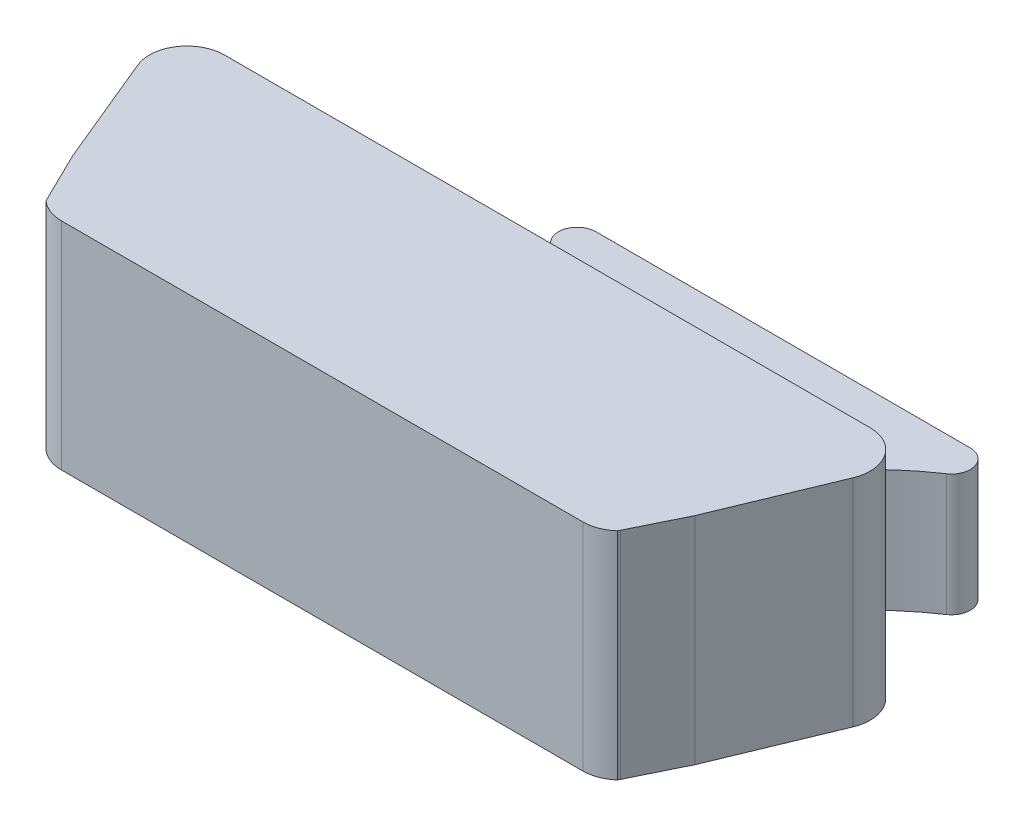
SolidWorks part; units mm, degrees
ref_plane "前视基准面" through (0, 0, 0) normal (0, 0, 1) x (1, 0, 0)
ref_plane "上视基准面" through (0, 0, 0) normal (0, 1, 0) x (1, 0, 0)
ref_plane "右视基准面" through (0, 0, 0) normal (1, 0, 0) x (0, 0, -1)
other "Configuration Table"
sketch "草图1" plane through (0, 0, 0) normal (0, 1, 0) x (1, 0, 0)
  line L0 (0, 0) -> (0, 18.74) construction
  line L1 (-14.3085, 18.74) -> (14.3085, 18.74)
  line L2 (3.9, 4.46) -> (3.9, 0)
  line L3 (-3.9, 0) -> (3.9, 0)
  line L4 (-3.9, 4.46) -> (-3.9, 0)
  arc A0 (14.3085, 18.74) -> (3.9, 4.46) centre (18.9, 4.46) ccw
  arc A1 (-14.3085, 18.74) -> (-3.9, 4.46) centre (-18.9, 4.46) cw
  dimension "D2" = 15
  dimension "D1" = 7.8
  dimension "D3" = 14.28
  dimension "D4" = 18.74
extrude "凸台-拉伸1" add sketch "草图1" along normal blind 6.5
sketch "草图2" plane through (0, 6.5, 0) normal (0, 1, 0) x (1, 0, 0)
  line L0 (9.9174, 1.2346) -> (13.2311, 9.2346) construction
  line L1 (11.3833, 12) -> (-23.0327, 12) construction
  line L2 (-24.8805, 9.2346) -> (-21.5668, 1.2346) construction
  line L3 (-19.719, 0) -> (8.0696, 0) construction
  line L4 (10.7621, 3.274) -> (13.2311, 9.2346)
  line L5 (11.3833, 12) -> (-23.0327, 12)
  line L6 (-24.8805, 9.2346) -> (-22.4115, 3.274)
  line L7 (-19.719, 0) -> (8.0696, 0)
  line L8 (14.1206, 10.119) -> (9.4595, 0.619) construction
  line L9 (-21.1089, 0.619) -> (-25.7699, 10.119) construction
  line L10 (10.7621, 3.274) -> (9.4595, 0.619)
  line L11 (-21.1089, 0.619) -> (-22.4115, 3.274)
  arc A1 (8.0696, 0) -> (9.9174, 1.2346) centre (8.0696, 2) ccw construction
  arc A2 (13.2311, 9.2346) -> (11.3833, 12) centre (11.3833, 10) ccw construction
  arc A3 (-23.0327, 12) -> (-24.8805, 9.2346) centre (-23.0327, 10) ccw construction
  arc A4 (-21.5668, 1.2346) -> (-19.719, 0) centre (-19.719, 2) ccw construction
  arc A5 (8.0696, 0) -> (9.3997, 0.5064) centre (8.0696, 2) ccw
  arc A6 (13.2311, 9.2346) -> (11.3833, 12) centre (11.3833, 10) ccw
  arc A7 (-23.0327, 12) -> (-24.8805, 9.2346) centre (-23.0327, 10) ccw
  arc A8 (-21.0491, 0.5064) -> (-19.719, 0) centre (-19.719, 2) ccw
  arc A9 (-21.1089, 0.619) -> (-19.3134, -0.5) centre (-19.3134, 1.5) ccw construction
  arc A10 (-21.1089, 0.619) -> (-21.0491, 0.5064) centre (-19.3134, 1.5) ccw
  arc A11 (7.664, -0.5) -> (9.4595, 0.619) centre (7.664, 1.5) ccw construction
  arc A12 (9.3997, 0.5064) -> (9.4595, 0.619) centre (7.664, 1.5) ccw
extrude "凸台-拉伸2" add sketch "草图2" along normal blind 5
fillet "圆角1" radius 1 4 edges at (3.9, 3.25, 0) (-3.9, 3.25, 0) (14.3085, 3.25, -18.74) (-14.3085, 3.25, -18.74)
extrude "凸台-拉伸3" add sketch "草图2<2>" against normal up to surface (6.5 mm away) up to face at (0, 0, -8.3876)
sketch "草图2<2>" plane through (0, 6.5, 0) normal (0, 1, 0) x (1, 0, 0) same geometry as "草图2"
